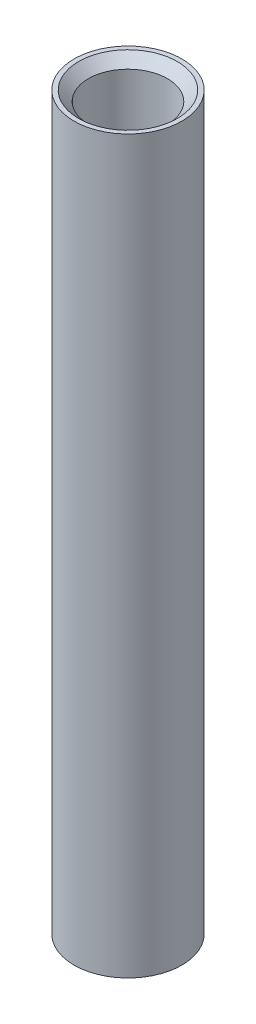
SolidWorks part; units mm, degrees
material "Natural Rubber"
ref_plane "Front Plane" through (0, 0, 0) normal (0, 0, 1) x (1, 0, 0)
ref_plane "Top Plane" through (0, 0, 0) normal (0, 1, 0) x (1, 0, 0)
ref_plane "Right Plane" through (0, 0, 0) normal (1, 0, 0) x (0, 0, -1)
sketch "Sketch1" plane through (0, 0, 0) normal (0, 1, 0) x (1, 0, 0)
  circle A0 centre (0, 0) radius 27.3
  circle A1 centre (0, 0) radius 20
  dimension "D1" = 54.6
  dimension "D2" = 40
extrude "Boss-Extrude1" add sketch "Sketch1" along normal blind 370.2
chamfer "Chamfer2" distance 5 angle 45 1 edges at (0, 370.2, 20)
